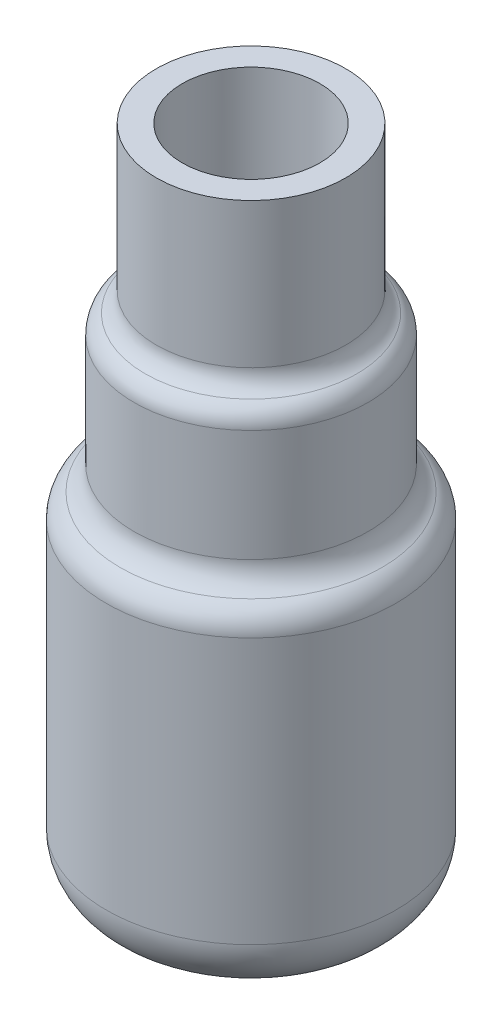
SolidWorks part; units mm, degrees
ref_plane "Спереди" through (0, 0, 0) normal (0, 0, 1) x (1, 0, 0)
ref_plane "Сверху" through (0, 0, 0) normal (0, 1, 0) x (1, 0, 0)
ref_plane "Справа" through (0, 0, 0) normal (1, 0, 0) x (0, 0, -1)
sketch "Эскиз1" plane through (0, 0, 0) normal (0, 1, 0) x (1, 0, 0)
  circle A0 centre (0, 0) radius 21
  circle A1 centre (0, 0) radius 26
  dimension "D1" = 42
  dimension "D2" = 52
extrude "Вытянуть1" add sketch "Эскиз1" along normal blind 60
fillet "Скругление1" radius 10 1 edges at (0, 0, 26)
sketch "Эскиз2" plane through (0, 60, 0) normal (0, 1, 0) x (1, 0, 0)
  circle A0 centre (0, 0) radius 21
  circle A1 centre (0, 0) radius 12.35
  dimension "D1" = 24.7
  dimension "D2" = 42
extrude "Вытянуть2" add sketch "Эскиз2" along normal blind 30 from offset 2 offset against normal yes
sketch "Эскиз3" plane through (0, 88, 0) normal (0, 1, 0) x (1, 0, 0)
  circle A0 centre (0, 0) radius 12.35
  circle A1 centre (0, 0) radius 17
  dimension "D1" = 24.7
extrude "Вытянуть3" add sketch "Эскиз3" along normal blind 30
fillet "Скругление3" radius 4 1 edges at (0, 88, 17)
fillet "Скругление4" radius 4 1 edges at (0, 88, 21)
fillet "Скругление6" radius 5 1 edges at (0, 60, 21)
fillet "Скругление7" radius 5 1 edges at (0, 60, 26)
fillet "Скругление8" radius 5 1 edges at (0, 58, 21)
fillet "Скругление9" radius 5 1 edges at (0, 58, 12.35)
